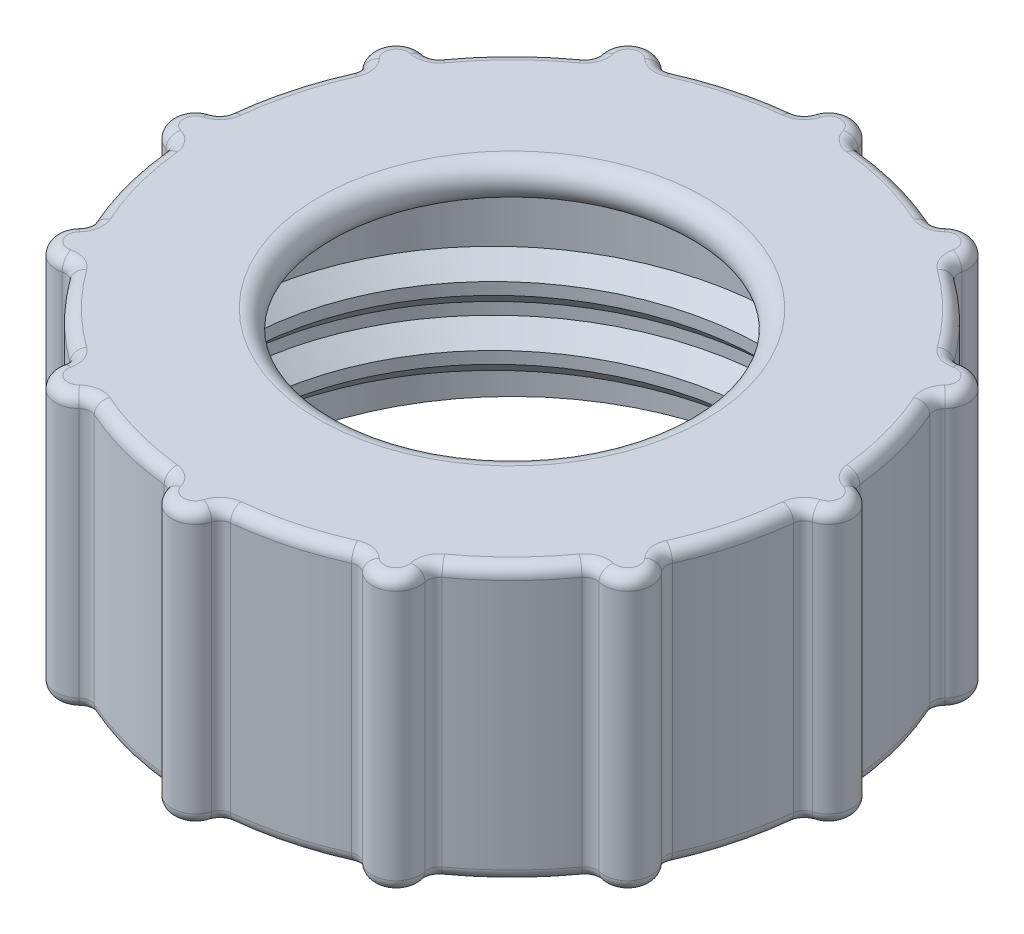
SolidWorks part; units mm, degrees
ref_plane "前视基准面" through (0, 0, 0) normal (0, 0, 1) x (1, 0, 0)
ref_plane "上视基准面" through (0, 0, 0) normal (0, 1, 0) x (1, 0, 0)
ref_plane "右视基准面" through (0, 0, 0) normal (1, 0, 0) x (0, 0, -1)
other "Configuration Table"
sketch "草图1" plane through (0, 0, 0) normal (0, 0, 1) x (1, 0, 0)
  line L0 (0, -5338.8039) -> (0, 261601.3908) construction
  line L1 (0, 32.3027) -> (0, 28.3027)
  line L7 (0, 0) -> (-18.1735, 0) construction
  line L8 (-18.1735, 0) -> (-12.4, 10) construction
  line L9 (-12.4, 10) -> (0, 10) construction
  line L10 (-18.1735, 0) -> (-23.5, 0) construction
  line L11 (-23.5, 0) -> (-23.5, -23.1259) construction
  line L12 (-23.5, 5) -> (0, 5) construction
  line L13 (-16.1528, 8) -> (-23.5, 8)
  line L14 (-23.5, 8) -> (-26.5, 8)
  line L15 (-26.5, 8) -> (-26.5, -15)
  line L16 (-26.5, -15) -> (-23.5, -15)
  line L17 (-23.5, -15) -> (-23.5, 0)
  line L18 (-23.5, 0) -> (-18.5, 5)
  line L19 (-18.5, 5) -> (-16.1528, 5)
  arc A1 (-16.1528, 5) -> (-16.1528, 8) centre (-16.1528, 6.5) ccw
  point P6 (-17.9412, 5.1954)
  dimension "D1" = 5
  dimension "D2" = 60
  dimension "D3" = 12.4
  dimension "D4" = 10
  dimension "D5" = 23.5
  dimension "D6" = 45
  dimension "D7" = 3
  dimension "D8" = 3
  dimension "D9" = 15
revolve "旋转1" add sketch "草图1" angle 360 about L0 region at (-14.9115, 6.5, 0)
ref_plane "基准面1" through (0, -13, 0) normal (0, -1, 0) x (-1, 0, 0)
sketch "草图2" plane through (0, -13, 0) normal (0, -1, 0) x (-1, 0, 0)
  circle A0 centre (0, 0) radius 23.5 construction
  circle A1 centre (0, 0) radius 23.5
curve "螺旋线/涡状线1" pitch 5 height 10 radius 23.5 centre (0, -13, 0) axis (0, 1, 0) start towards (1, 0, 0)
sketch "草图3" plane through (0, 0, 0) normal (0, 0, 1) x (1, 0, 0)
  line L0 (-23.5, 0) -> (-23.5, -15)
  line L1 (23.5, -15) -> (23.5, 0)
  line L2 (23.5, -15) -> (23.5, -11)
  line L3 (-23.5, 0) -> (-23.5, -15)
  line L4 (23.5, -11) -> (22, -12.5)
  line L5 (22, -12.5) -> (22, -13.5)
  line L6 (22, -13.5) -> (23.5, -15)
  point P11 (23.5, -13)
  dimension "D1" = 45
  dimension "D2" = 45
  dimension "D3" = 4
  dimension "D4" = 1.5
sweep "扫描2" add profiles "草图3" path "螺旋线/涡状线1"
sketch "草图7" plane through (0, 8, 0) normal (0, 1, 0) x (1, 0, 0)
  circle A0 centre (0, 0) radius 26.5 construction
  arc A1 (-2.7727, 26.3545) -> (2.7727, 26.3545) centre (0, 0) ccw
  arc A2 (1.9182, 27.066) -> (-1.9182, 27.066) centre (0, 26.5) ccw
  arc A3 (-2.7727, 26.3545) -> (-1.9182, 27.066) centre (-2.8773, 27.3491) ccw
  arc A4 (1.9182, 27.066) -> (2.7727, 26.3545) centre (2.8773, 27.3491) ccw
  circle A5 centre (0, 0) radius 26.5
  circle M1 centre (0, 0) radius 26.5
  dimension "D1" = 4
  dimension "D2" = 1
  dimension "D3" = 1
extrude "凸台-拉伸1" add sketch "草图7" against normal up to surface (23 mm away) contours A2 M1 region at (0, 8, -27.3101) up to face at (23.5, -15, 0)
pattern_circular "阵列(圆周)1" count 12 over 360 about axis through (0, 8, 0) along (0, -1, 0) of "凸台-拉伸1"
fillet "圆角1" radius 1 1 edges at (18.7383, 8, -18.7383)
fillet "圆角2" radius 1 5 edges at (2.2375, -15, -26.5806) (0, -15, -28.5) (-2.2375, -15, -26.5806) (-6.8587, -15, -25.597) (6.8587, -15, -25.597)
